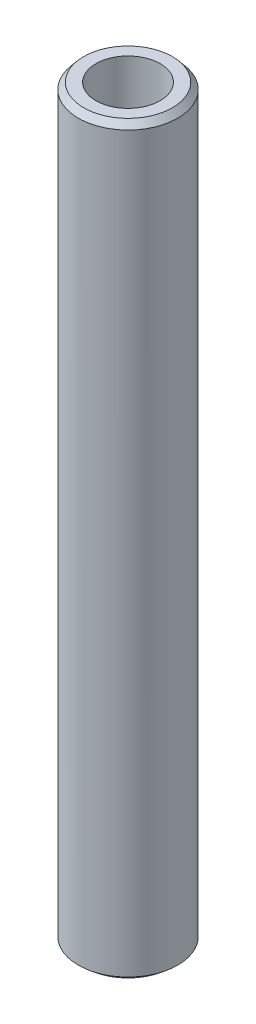
SolidWorks part; units mm, degrees
ref_plane "Front Plane" through (0, 0, 0) normal (0, 0, 1) x (1, 0, 0)
ref_plane "Top Plane" through (0, 0, 0) normal (0, 1, 0) x (1, 0, 0)
ref_plane "Right Plane" through (0, 0, 0) normal (1, 0, 0) x (0, 0, -1)
sketch "Sketch1" plane through (0, 0, 0) normal (0, 1, 0) x (1, 0, 0)
  circle A0 centre (0, 0) radius 40
  dimension "SHAFT_OD" = 80
extrude "Boss-Extrude1" add sketch "Sketch1" along normal blind 600
sketch "Sketch2" plane through (0, 0, 0) normal (0, 1, 0) x (1, 0, 0)
  circle A0 centre (0, 0) radius 25.8744
  dimension "BORE_D" = 51.7487
extrude "Cut-Extrude1" cut sketch "Sketch2" along normal through all
chamfer "Chamfer1" distance 5.1306 angle 39.886 2 edges at (0, 600, 40) (0, 0, 40) first distance on face at (0, 600, 40) first distance on face at (0, 0, 25.8744)
